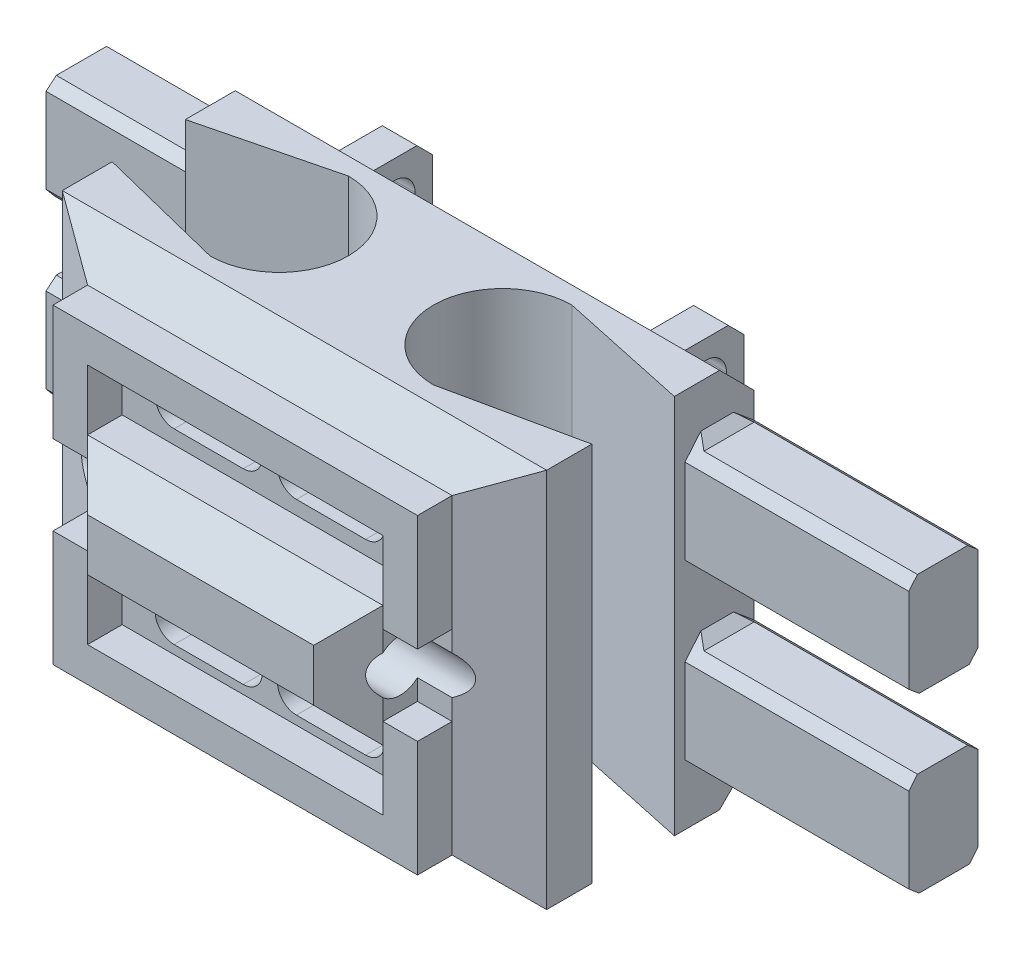
SolidWorks part; units mm, degrees
ref_plane "Front Plane" through (0, 0, 0) normal (0, 0, 1) x (1, 0, 0)
ref_plane "Top Plane" through (0, 0, 0) normal (0, 1, 0) x (1, 0, 0)
ref_plane "Right Plane" through (0, 0, 0) normal (1, 0, 0) x (0, 0, -1)
sketch "Base" plane through (0, 0, 0) normal (0, 0, 1) x (1, 0, 0)
  line L1 (0, 0) -> (14, 0)
  line L2 (0, 0) -> (0, 11)
  line L3 (0, 11) -> (14, 11)
  line L4 (14, 0) -> (14, 11)
  dimension "D1" = 14
  dimension "D2" = 11
extrude "Boss-Extrude1" add sketch "Base" along normal blind 7
chamfer "Chamfer4" distance 1 angle 45 2 edges at (7, 11, 7) (7, 0, 7)
chamfer "Chamfer5" distance 1 angle 60 2 edges at (0, 5.5, 7) (14, 5.5, 7)
chamfer "Chamfer6" distance 1 angle 45 2 edges at (7, 11, 0) (7, 0, 0)
sketch "Tendon extrude" plane through (0, 0, 0) normal (0, -1, 0) x (1, 0, 0)
  line L0 (7, 6) -> (7, -3.9632) construction
  line L1 (14, 6) -> (0, 6) construction
  line L2 (0, 3.5) -> (21.7648, 3.5) construction
  line L3 (0, 6) -> (0, 1) construction
  line L4 (3.77, 3.5) -> (-2.23, 3.5) construction
  line L5 (-2.23, 3) -> (-2.23, 4)
  line L6 (3.77, 5.5) -> (-2.23, 4)
  line L7 (-2.23, 3) -> (3.77, 1.5)
  line L10 (10.23, 3.5) -> (17.23, 3.5) construction
  line L11 (17.23, 3) -> (17.23, 4)
  line L12 (10.23, 5.5) -> (17.23, 4)
  line L13 (17.23, 3) -> (10.23, 1.5)
  circle A0 centre (3.77, 3.5) radius 2
  circle A1 centre (10.23, 3.5) radius 2
  dimension "D1" = 4
  dimension "D2" = 3.77
  dimension "D3" = 1
  dimension "D4" = 6
  dimension "D5" = 1
  dimension "D6" = 7
sketch "Sketch8" plane through (0, 0, 7) normal (0, 0, 1) x (1, 0, 0)
  line L0 (12.2679, 5.5) -> (1.7321, 5.5) construction
  line L1 (12.2679, 1) -> (12.2679, 10) construction
  line L2 (1.7321, 10) -> (1.7321, 1) construction
  line L3 (7, 1) -> (7, 10) construction
  line L4 (1.7321, 1) -> (12.2679, 1) construction
  line L5 (12.2679, 10) -> (1.7321, 10) construction
  line L6 (2.7321, 3.75) -> (2.7321, 7.25)
  line L7 (11.2679, 7.25) -> (2.7321, 7.25)
  line L8 (11.2679, 7.25) -> (11.2679, 3.75)
  line L9 (11.2679, 3.75) -> (2.7321, 3.75)
  point P17 (2.7321, 5.5)
  point P18 (11.2679, 5.5)
  dimension "D1" = 1.75
  dimension "D2" = 1
  dimension "D3" = 1
extrude "Boss-Extrude5" add sketch "Sketch8" along normal blind 2
sketch "Sketch9" plane through (11.2679, 0, 0) normal (1, 0, 0) x (0, 0, -1)
  line L0 (-9, 5.5) -> (-7, 5.5) construction
  line L1 (-9, 3.75) -> (-9, 7.25) construction
  line L2 (-7, 3.75) -> (-7, 7.25) construction
  circle A0 centre (-7.5, 5.5) radius 0.75
  dimension "D1" = 1.5
  dimension "D2" = 1.5
extrude "Cut-Extrude5" cut sketch "Sketch9" against normal blind 34.5 and the other way blind 4.2544
chamfer "Chamfer9" distance 1 angle 45 4 edges at (2.7321, 5.5, 9) (7, 7.25, 9) (11.2679, 5.5, 9) (7, 3.75, 9)
sketch "Sketch13" plane through (0, 0, 0) normal (0, 0, -1) x (-1, 0, 0)
  line L0 (0, 5.5) -> (-33.4926, 5.5) construction
  line L1 (0, 10) -> (0, 1) construction
  line L2 (-7, 1) -> (-7, 15.915) construction
  line L3 (-14, 1) -> (0, 1) construction
  line L4 (-1, 7.25) -> (-6, 7.25)
  line L5 (-8, 7.25) -> (-8, 3.75)
  line L6 (-1, 7.25) -> (-1, 3.75)
  line L7 (-1, 3.75) -> (-6, 3.75)
  line L8 (-6, 7.25) -> (-6, 3.75)
  line L9 (-13, 7.25) -> (-8, 7.25)
  line L10 (-13, 3.75) -> (-8, 3.75)
  line L11 (-13, 7.25) -> (-13, 3.75)
  point P13 (-6, 5.5)
  point P14 (-1, 5.5)
  dimension "D1" = 1.75
  dimension "D2" = 1
  dimension "D3" = 5
extrude "Boss-Extrude6" add sketch "Sketch13" along normal blind 2
chamfer "Chamfer10" distance 1 angle 45 8 edges at (8, 5.5, -2) (10.5, 3.75, -2) (13, 5.5, -2) (10.5, 7.25, -2) (3.5, 7.25, -2) (1, 5.5, -2) (3.5, 3.75, -2) (6, 5.5, -2)
sketch "Sketch14" plane through (1, 0, 0) normal (-1, 0, 0) x (0, 0, 1)
  line L0 (-1, 5.5) -> (0, 5.5) construction
  line L1 (-1, 7.25) -> (-1, 3.75) construction
  line L2 (0, 3.75) -> (0, 7.25) construction
  line L3 (-2, 4.75) -> (-2, 6.25) construction
  circle A0 centre (-0.5, 5.5) radius 0.75
  dimension "D1" = 1.5
  dimension "D2" = 1.5
extrude "Cut-Extrude6" cut sketch "Sketch14" against normal blind 30 and the other way blind 3
sketch "Sketch15" plane through (0, 0, 0) normal (0, 0, -1) x (-1, 0, 0)
  line L0 (-12, 4.75) -> (-9, 4.75) construction
  line L1 (-12, 1) -> (-11, 1)
  line L2 (-12, 1) -> (-12, 4.75)
  line L3 (-12, 4.75) -> (-11, 4.75)
  line L4 (-11, 1) -> (-11, 4.75)
  line L5 (-12, 6.25) -> (-12, 4.75) construction
  line L6 (-7, 1) -> (-7, 10) construction
  line L7 (-14, 1) -> (0, 1) construction
  line L8 (0, 10) -> (-14, 10) construction
  line L9 (-9, 6.25) -> (-12, 6.25) construction
  line L10 (-12, 6.25) -> (-11, 6.25)
  line L11 (-12, 6.25) -> (-12, 10)
  line L12 (-12, 10) -> (-11, 10)
  line L13 (-11, 6.25) -> (-11, 10)
  line L14 (-2, 1) -> (-3, 1)
  line L15 (-2, 1) -> (-2, 4.75)
  line L16 (-3, 1) -> (-3, 4.75)
  line L17 (-2, 4.75) -> (-3, 4.75)
  line L18 (-2, 6.25) -> (-3, 6.25)
  line L19 (-2, 10) -> (-3, 10)
  line L20 (-3, 6.25) -> (-3, 10)
  line L21 (-2, 6.25) -> (-2, 10)
  dimension "D1" = 0
  dimension "D3" = 1
  dimension "D4" = 0
  dimension "D5" = 0
extrude "Boss-Extrude7" add sketch "Sketch15" along normal blind 2
sketch "Sketch16" plane through (12, 0, 0) normal (1, 0, 0) x (0, 0, -1)
  line L0 (0.6, 3.15) -> (0.6, 2.15) construction
  line L1 (1.2, 3.15) -> (1.2, 2.15)
  line L2 (0, 3.15) -> (0, 2.15)
  line L3 (1, 3.75) -> (0, 3.75) construction
  line L5 (0.6, 7.85) -> (0.6, 8.85) construction
  line L6 (0, 7.85) -> (0, 8.85)
  line L7 (1.2, 7.85) -> (1.2, 8.85)
  line L9 (1, 7.25) -> (0, 7.25) construction
  line L10 (0, 3.75) -> (0, 1) construction
  arc A0 (1.2, 3.15) -> (0, 3.15) centre (0.6, 3.15) ccw
  arc A1 (0, 2.15) -> (1.2, 2.15) centre (0.6, 2.15) ccw
  arc A2 (0, 7.85) -> (1.2, 7.85) centre (0.6, 7.85) ccw
  arc A3 (1.2, 8.85) -> (0, 8.85) centre (0.6, 8.85) ccw
  point P2 (0.6, 2.65)
  point P13 (0.6, 8.35)
  point P20 (0.5, 7.25)
  dimension "D1" = 1
  dimension "D2" = 0.6
  dimension "D3" = 0.6
  dimension "D4" = 0
  dimension "D5" = 0.6
extrude "Cut-Extrude7" cut sketch "Sketch16" against normal blind 26
chamfer "Chamfer11" distance 0.3 angle 45 8 edges at (2, 2.875, -2) (3, 2.875, -2) (3, 8.125, -2) (2, 8.125, -2) (12, 8.125, -2) (11, 8.125, -2) (12, 2.875, -2) (11, 2.875, -2)
chamfer "Chamfer12" distance 0.75 angle 45 4 edges at (11.5, 1, -2) (11.5, 10, -2) (2.5, 10, -2) (2.5, 1, -2)
extrude "Cut-Extrude8" cut sketch "Tendon extrude" against normal up to surface (11 mm away)
sketch "Sketch18" plane through (14, 0, 0) normal (1, 0, 0) x (0, 0, -1)
  line L0 (-2.3079, 5.5) -> (-0.25, 5.5) construction
  line L1 (-2.3079, 11) -> (-2.3079, 0) construction
  line L3 (-2, 6.5) -> (0, 6.5)
  line L4 (-2, 6.5) -> (-2, 9.5)
  line L5 (-2, 9.5) -> (0, 9.5)
  line L6 (0, 6.5) -> (0, 9.5)
  line L7 (-2, 4.5) -> (0, 4.5)
  line L8 (0, 4.5) -> (0, 1.5)
  line L9 (-2, 1.5) -> (0, 1.5)
  line L10 (-2, 4.5) -> (-2, 1.5)
  line L11 (0, 6.059) -> (0, 10) construction
  arc A0 (0, 6.059) -> (0, 4.941) centre (0.5, 5.5) ccw construction
  dimension "D1" = 3
  dimension "D2" = 2
  dimension "D3" = 1
extrude "Boss-Extrude8" add sketch "Sketch18" along normal blind 6.47
chamfer "Chamfer13" distance 0.25 angle 50 8 edges at (17.235, 1.5, 2) (17.235, 4.5, 2) (17.235, 6.5, 2) (17.235, 9.5, 2) (17.235, 9.5, 0) (17.235, 6.5, 0) (17.235, 4.5, 0) (17.235, 1.5, 0)
chamfer "Chamfer14" distance 0.25 angle 50 4 edges at (14, 9.5, 1.024) (14, 1.5, 0.976) (14, 4.5, 1.024) (14, 6.5, 0.976)
sketch "Sketch19" plane through (0, 0, 0) normal (-1, 0, 0) x (0, 0, 1)
  line L0 (0.25, 5.5) -> (2.4425, 5.5) construction
  line L1 (2.4425, 11) -> (2.4425, 0) construction
  line L3 (0, 4.5) -> (2, 4.5)
  line L4 (0, 4.5) -> (0, 1.5)
  line L5 (0, 1.5) -> (2, 1.5)
  line L6 (2, 4.5) -> (2, 1.5)
  line L7 (2, 6.5) -> (2, 9.5)
  line L8 (0, 9.5) -> (2, 9.5)
  line L9 (0, 6.5) -> (0, 9.5)
  line L10 (0, 6.5) -> (2, 6.5)
  line L11 (0, 4.941) -> (0, 1) construction
  arc A0 (0, 4.941) -> (0, 6.059) centre (-0.5, 5.5) ccw construction
  dimension "D1" = 2
  dimension "D2" = 3
  dimension "D4" = 1
extrude "Boss-Extrude9" add sketch "Sketch19" along normal blind 4.47
chamfer "Chamfer15" distance 0.25 angle 50 8 edges at (-2.235, 1.5, 2) (-2.235, 4.5, 2) (-2.235, 9.5, 2) (-2.235, 6.5, 2) (-2.235, 1.5, 0) (-2.235, 4.5, 0) (-2.235, 9.5, 0) (-2.235, 6.5, 0)
chamfer "Chamfer16" distance 0.25 angle 50 4 edges at (0, 9.5, 0.976) (0, 6.5, 1.024) (0, 4.5, 0.976) (0, 1.5, 1.024)
sketch "Sketch20" plane through (0, 0, 7) normal (0, 0, 1) x (1, 0, 0)
  line L0 (12.2679, 6.059) -> (12.2679, 10) construction
  line L1 (1.7321, 10) -> (12.2679, 10)
  line L2 (1.7321, 10) -> (1.7321, 9)
  line L3 (1.7321, 9) -> (12.2679, 9)
  line L4 (12.2679, 10) -> (12.2679, 9)
  line L5 (2.7321, 7.25) -> (2.7321, 6.059) construction
  line L6 (2.7321, 6.6545) -> (1.7321, 6.6545)
  line L7 (2.7321, 6.6545) -> (2.7321, 9)
  line L8 (2.7321, 9) -> (1.7321, 9)
  line L9 (1.7321, 6.6545) -> (1.7321, 9)
  line L10 (11.2679, 6.059) -> (11.2679, 7.25) construction
  line L11 (11.2679, 6.6545) -> (12.2679, 6.6545)
  line L12 (11.2679, 6.6545) -> (11.2679, 9)
  line L13 (11.2679, 9) -> (12.2679, 9)
  line L14 (12.2679, 6.6545) -> (12.2679, 9)
  line L15 (1.7321, 4.941) -> (1.7321, 1) construction
  line L16 (12.2679, 1) -> (1.7321, 1)
  line L17 (12.2679, 1) -> (12.2679, 2)
  line L18 (12.2679, 2) -> (1.7321, 2)
  line L19 (1.7321, 1) -> (1.7321, 2)
  line L20 (2.7321, 4.941) -> (2.7321, 3.75) construction
  line L21 (2.7321, 4.3455) -> (1.7321, 4.3455)
  line L22 (2.7321, 4.3455) -> (2.7321, 2)
  line L23 (2.7321, 2) -> (1.7321, 2)
  line L24 (1.7321, 4.3455) -> (1.7321, 2)
  line L25 (11.2679, 3.75) -> (11.2679, 4.941) construction
  line L26 (12.2679, 2) -> (11.2679, 2)
  line L27 (12.2679, 2) -> (12.2679, 4.3455)
  line L28 (12.2679, 4.3455) -> (11.2679, 4.3455)
  line L29 (11.2679, 2) -> (11.2679, 4.3455)
  line M2 (12.2679, 6.059) -> (12.2679, 10)
  line M3 (12.2679, 10) -> (1.7321, 10)
  line M4 (1.7321, 10) -> (1.7321, 6.059)
  line M6 (2.7321, 6.059) -> (2.7321, 7.25)
  line M8 (11.2679, 7.25) -> (11.2679, 6.059)
extrude "Boss-Extrude10" add sketch "Sketch20" along normal blind 1 contours L7 L3 L6 M6 M4 | L3 M4 M2 M3 | L12 L11 L3 M8 M2 | L29 L18 L27 L28 | L19 L16 L17 L18 | L21 L24 L18 L22
sketch "Sketch21" plane through (0, 0, 7) normal (0, 0, 1) x (1, 0, 0)
  line L0 (4.2321, 8.2) -> (6.2321, 8.2) construction
  line L1 (4.2321, 8.7469) -> (6.2321, 8.7469)
  line L2 (4.2321, 7.6531) -> (6.2321, 7.6531)
  line L3 (7.7679, 8.2) -> (9.7679, 8.2) construction
  line L4 (7.7679, 8.7469) -> (9.7679, 8.7469)
  line L5 (7.7679, 7.6531) -> (9.7679, 7.6531)
  line L6 (7.7679, 2.8) -> (9.7679, 2.8) construction
  line L7 (7.7679, 3.3469) -> (9.7679, 3.3469)
  line L8 (7.7679, 2.2531) -> (9.7679, 2.2531)
  line L9 (6.2321, 2.8) -> (4.2321, 2.8) construction
  line L10 (6.2321, 2.2531) -> (4.2321, 2.2531)
  line L11 (6.2321, 3.3469) -> (4.2321, 3.3469)
  line L12 (2.7321, 9) -> (11.2679, 9) construction
  line L13 (11.2679, 2) -> (2.7321, 2) construction
  line L14 (2.7321, 7.25) -> (2.7321, 9) construction
  line L15 (11.2679, 7.25) -> (11.2679, 9) construction
  arc A0 (4.2321, 8.7469) -> (4.2321, 7.6531) centre (4.2321, 8.2) ccw
  arc A1 (6.2321, 7.6531) -> (6.2321, 8.7469) centre (6.2321, 8.2) ccw
  arc A2 (7.7679, 8.7469) -> (7.7679, 7.6531) centre (7.7679, 8.2) ccw
  arc A3 (9.7679, 7.6531) -> (9.7679, 8.7469) centre (9.7679, 8.2) ccw
  arc A4 (7.7679, 3.3469) -> (7.7679, 2.2531) centre (7.7679, 2.8) ccw
  arc A5 (9.7679, 2.2531) -> (9.7679, 3.3469) centre (9.7679, 2.8) ccw
  arc A6 (6.2321, 2.2531) -> (6.2321, 3.3469) centre (6.2321, 2.8) ccw
  arc A7 (4.2321, 3.3469) -> (4.2321, 2.2531) centre (4.2321, 2.8) ccw
  point P2 (5.2321, 8.2)
  point P7 (8.7679, 8.2)
  point P14 (8.7679, 2.8)
  point P21 (5.2321, 2.8)
  point P32 (2.7321, 8.125)
  point P35 (11.2679, 8.125)
  dimension "D1" = 0.8
  dimension "D2" = 0.8
  dimension "D3" = 2
  dimension "D4" = 1.5
  dimension "D5" = 1.5
extrude "Cut-Extrude9" cut sketch "Sketch21" against normal blind 1
